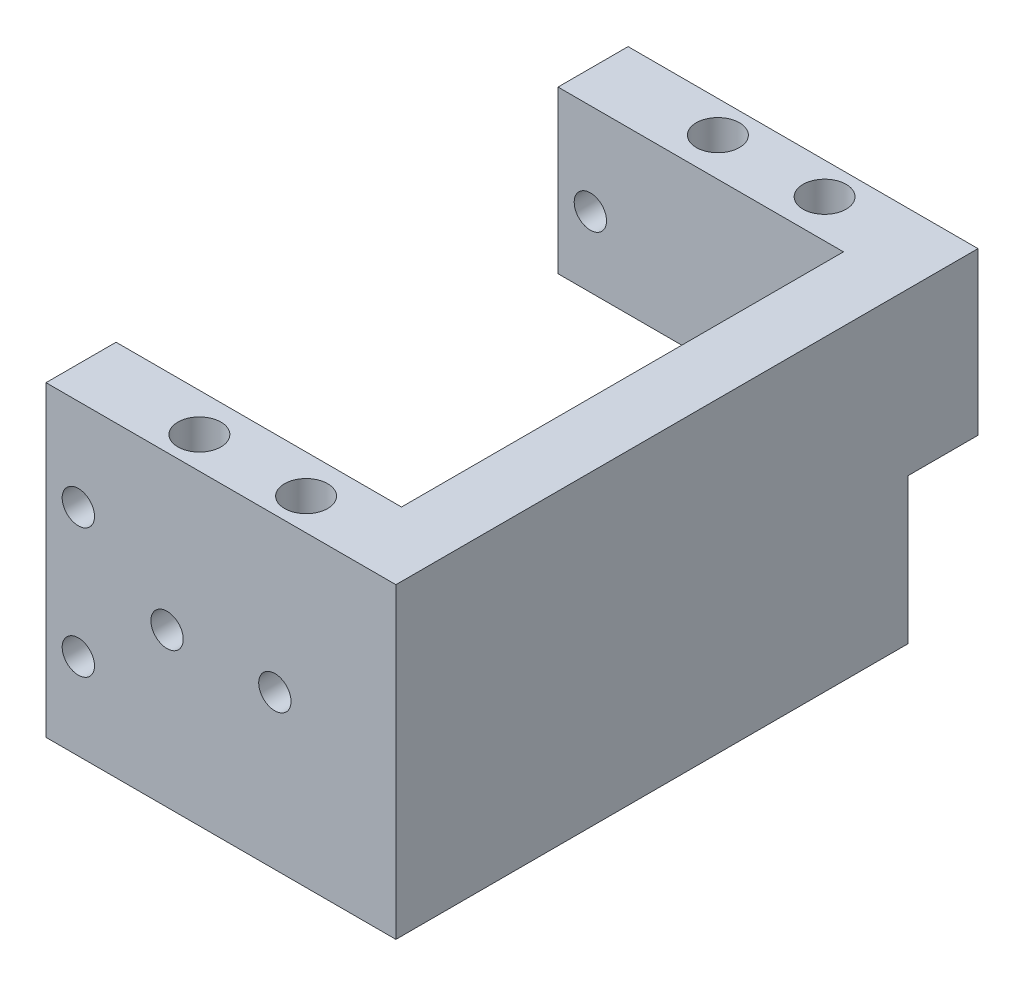
SolidWorks part; units mm, degrees
ref_plane "Front Plane" through (0, 0, 0) normal (0, 0, 1) x (1, 0, 0)
ref_plane "Top Plane" through (0, 0, 0) normal (0, 1, 0) x (1, 0, 0)
ref_plane "Right Plane" through (0, 0, 0) normal (1, 0, 0) x (0, 0, -1)
sketch "Sketch2" plane through (0, 0, 0) normal (0, 1, 0) x (1, 0, 0)
  line L0 (0, 37.811) -> (0, -32.5623)
  line L1 (-16.23, -23.75) -> (16.23, -23.75)
  line L2 (-16.23, -23.75) -> (-16.23, 23.75)
  line L3 (-16.23, 23.75) -> (16.23, 23.75)
  line L4 (16.23, -23.75) -> (16.23, 23.75)
  line L5 (-16.23, -23.75) -> (16.23, 23.75) construction
  line L6 (-16.23, 23.75) -> (16.23, -23.75) construction
  line L7 (-10.25, 23.75) -> (10.25, 23.75)
  line L8 (-10.25, 23.75) -> (-10.25, -17.25)
  line L9 (-10.25, -17.25) -> (10.25, -17.25)
  line L10 (10.25, 23.75) -> (10.25, -17.25)
  line L11 (-16.23, 23.75) -> (16.23, 23.75)
  line L12 (-16.23, 23.75) -> (-16.23, 30.25)
  line L13 (-16.23, 30.25) -> (16.23, 30.25)
  line L14 (16.23, 23.75) -> (16.23, 30.25)
  line L15 (-16.23, 3.25) -> (16.23, 3.25)
  line L16 (-16.23, -17.25) -> (16.23, -17.25)
  circle A0 centre (-4.95, 27.3) radius 2
  circle A1 centre (4.95, 27.3) radius 2
  circle A4 centre (4.95, -20.8) radius 2
  circle A5 centre (-4.95, -20.8) radius 2
  circle A6 centre (-13.23, 19.75) radius 1.5
  circle A7 centre (13.23, 19.75) radius 1.5
  circle A8 centre (13.23, -13.25) radius 1.5
  circle A9 centre (-13.23, -13.25) radius 1.5
  point P0 (0, 0)
  dimension "D7" = 4.95
  dimension "D8" = 3.55
  dimension "D9" = 4
  dimension "D11" = 3
  dimension "D13" = 3
  dimension "D1" = 47.5
  dimension "D2" = 32.46
  dimension "D3" = 5.98
  dimension "D4" = 5.98
  dimension "D5" = 6.5
  dimension "D6" = 6.5
  dimension "D10" = 27
  dimension "D12" = 4
extrude "Boss-Extrude1" add sketch "Sketch2" along normal blind 28.5 contours A9 | L2 L16 L8 L15 A9 | A6 | L2 L15 L8 L3 A6 | L10 L15 L4 L3 A7 | A7 | L10 L16 L4 L15 A8 | A8 | A4 | A5 | L16 L2 L1 L0 L9 A5 | L16 L9 L0 L1 L4 A4 region at (-13.2406, 0, -13.1176) region at (13.2406, 0, -13.1176) region at (8.543, 0, 20.4594) region at (-8.543, 0, 20.4594) region at (-13.2406, 0, 6.6176) region at (13.2406, 0, 6.6176) region at (4.95, 0, 20.8) region at (-4.95, 0, 20.8) region at (-13.23, 0, -19.75) region at (13.23, 0, -19.75) region at (13.23, 0, 13.25) region at (-13.23, 0, 13.25)
extrude "Cut-Extrude1" cut sketch "Sketch2<4>" along normal blind 15 contours A7 | A6 | A9 | A8 region at (-13.23, 0, -19.75) region at (13.23, 0, -19.75) region at (13.23, 0, 13.25) region at (-13.23, 0, 13.25)
sketch "Sketch2<4>" plane through (0, 0, 0) normal (0, 1, 0) x (1, 0, 0) same geometry as "Sketch2"
sketch "Sketch3" plane through (-16.23, 0, 0) normal (-1, 0, 0) x (0, 0, 1)
  line L1 (-23.75, 28.5) -> (-30.25, 28.5)
  line L2 (-23.75, 28.5) -> (-23.75, 13.5)
  line L3 (-23.75, 13.5) -> (-30.25, 13.5)
  line L4 (-30.25, 28.5) -> (-30.25, 13.5)
  dimension "D1" = 15
  dimension "D2" = 6.5
extrude "Boss-Extrude2" add sketch "Sketch3" against normal blind 32.46
extrude "Cut-Extrude2" cut sketch "Sketch2<5>" along normal blind 94.46 contours A0 | A1 region at (-4.95, 0, -27.3) region at (4.95, 0, -27.3)
sketch "Sketch2<5>" plane through (0, 0, 0) normal (0, 1, 0) x (1, 0, 0) same geometry as "Sketch2"
extrude "Cut-Extrude4" cut sketch "Sketch2<6>" along normal blind 8 contours A5 | A4 region at (4.95, 0, 20.8) region at (-4.95, 0, 20.8)
sketch "Sketch2<6>" plane through (0, 0, 0) normal (0, 1, 0) x (1, 0, 0) same geometry as "Sketch2"
sketch "Sketch5" plane through (0, 28.5, 0) normal (0, 1, 0) x (1, 0, 0)
  circle A0 centre (-4.95, -20.8) radius 2
  circle A1 centre (4.95, -20.8) radius 2
extrude "Cut-Extrude5" cut sketch "Sketch5" against normal blind 8
sketch "Sketch4" plane through (0, 0, 17.25) normal (0, 0, -1) x (-1, 0, 0)
  line L0 (-16.23, 28.5) -> (16.23, 28.5) construction
  line L1 (-10.25, 0) -> (10.25, 0)
  line L2 (-10.25, 0) -> (-10.25, 28.5)
  line L3 (-10.25, 28.5) -> (10.25, 28.5)
  line L4 (10.25, 0) -> (10.25, 28.5)
  line L5 (10.25, 28.5) -> (10.25, 0) construction
  line L6 (0, 28.5) -> (0, 0)
  line L7 (-10.25, 14.25) -> (10.25, 14.25)
  circle A0 centre (-5, 14.25) radius 1.5
  circle A1 centre (5, 14.25) radius 1.5
  circle A2 centre (-5, 14.25) radius 3
  circle A3 centre (5, 14.25) radius 3
  dimension "D1" = 3
  dimension "D2" = 5
  dimension "D3" = 6
extrude "Cut-Extrude3" cut sketch "Sketch4" against normal blind 10 contours L7 A0 | L7 A0 | A1 L7 | A1 L7 region at (5, 14.8866, 17.25) region at (5, 13.6134, 17.25) region at (-5, 14.8866, 17.25) region at (-5, 13.6134, 17.25)
extrude "Cut-Extrude6" cut sketch "Sketch4<3>" against normal blind 3.5 contours L7 A2 A0 | L7 A2 A0 | A3 L7 A1 | A3 L7 A1 region at (5, 17.1829, 17.25) region at (7.25, 14.1829, 17.25) region at (-5, 17.1829, 17.25) region at (-2.75, 14.1829, 17.25)
sketch "Sketch4<3>" plane through (0, 0, 17.25) normal (0, 0, -1) x (-1, 0, 0) same geometry as "Sketch4"
sketch "Sketch11" plane through (-16.23, 0, 0) normal (-1, 0, 0) x (0, 0, 1)
  line L0 (23.75, 28.5) -> (-30.25, 28.5) construction
  line L1 (-23.75, 0) -> (17.25, 0)
  line L2 (-23.75, 0) -> (-23.75, 28.5)
  line L3 (-23.75, 28.5) -> (17.25, 28.5)
  line L4 (17.25, 0) -> (17.25, 28.5)
extrude "Cut-Extrude7" cut sketch "Sketch11" against normal up to next
sketch "Sketch12" plane through (0, 0, -30.25) normal (0, 0, -1) x (-1, 0, 0)
  line L0 (-16.23, 28.5) -> (16.23, 28.5) construction
  line L6 (10.23, 28.5) -> (16.23, 28.5)
  line L7 (10.23, 28.5) -> (10.23, 0)
  line L8 (10.23, 0) -> (16.23, 0)
  line L9 (16.23, 28.5) -> (16.23, 0)
  circle A0 centre (13.23, 20) radius 1.5
  circle A2 centre (13.23, 8) radius 1.5
  dimension "D1" = 3
  dimension "D4" = 3
  dimension "D5" = 8.5
  dimension "D3" = 3
  dimension "D6" = 3
  dimension "D7" = 8
  dimension "D2" = 6
extrude "Cut-Extrude8" cut sketch "Sketch12" against normal blind 64 contours A0 | A2 region at (-13.23, 20, -30.25)
